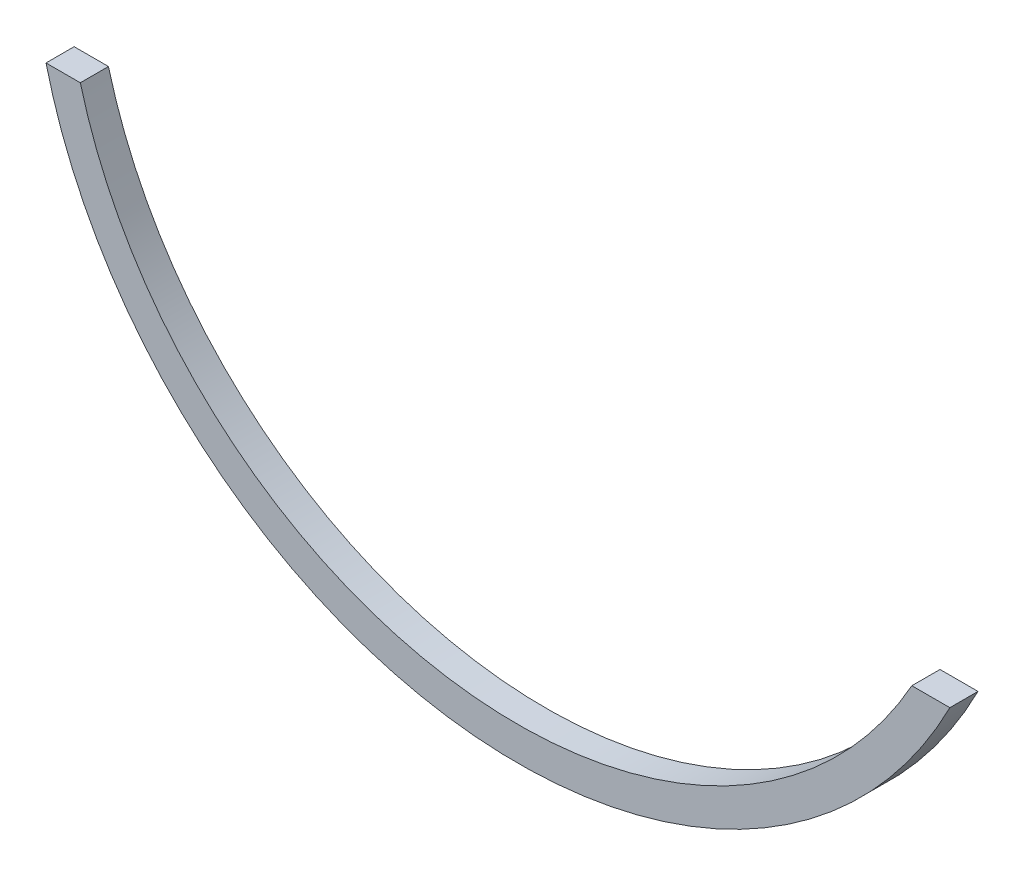
SolidWorks part; units mm, degrees
material "Hexcel AS4C (3000 Filaments)"
ref_plane "Front Plane" through (0, 0, 0) normal (0, 0, 1) x (1, 0, 0)
ref_plane "Top Plane" through (0, 0, 0) normal (0, 1, 0) x (1, 0, 0)
ref_plane "Right Plane" through (0, 0, 0) normal (1, 0, 0) x (0, 0, -1)
sketch "Sketch1" plane through (0, 0, 0) normal (0, 0, 1) x (1, 0, 0)
  line L0 (88.9044, -50) -> (97.4751, -50) construction
  line L1 (-106.3685, -26) -> (-98.6306, -26) construction
  line L2 (88.9044, -50) -> (97.4751, -50)
  line L3 (-106.3685, -26) -> (-98.6306, -26)
  circle A0 centre (0, 0) radius 109.5 construction
  circle A1 centre (0, 0) radius 102 construction
  circle A2 centre (0, 0) radius 109.5 construction
  circle A3 centre (0, 0) radius 102 construction
  arc A4 (-98.6306, -26) -> (88.9044, -50) centre (0, 0) ccw
  arc A6 (-106.3685, -26) -> (97.4751, -50) centre (0.0184, -0.0755) ccw
  point P2 (-215.2877, 37.8865)
extrude "Boss-Extrude1" add sketch "Sketch1" along normal mid plane 6.35
